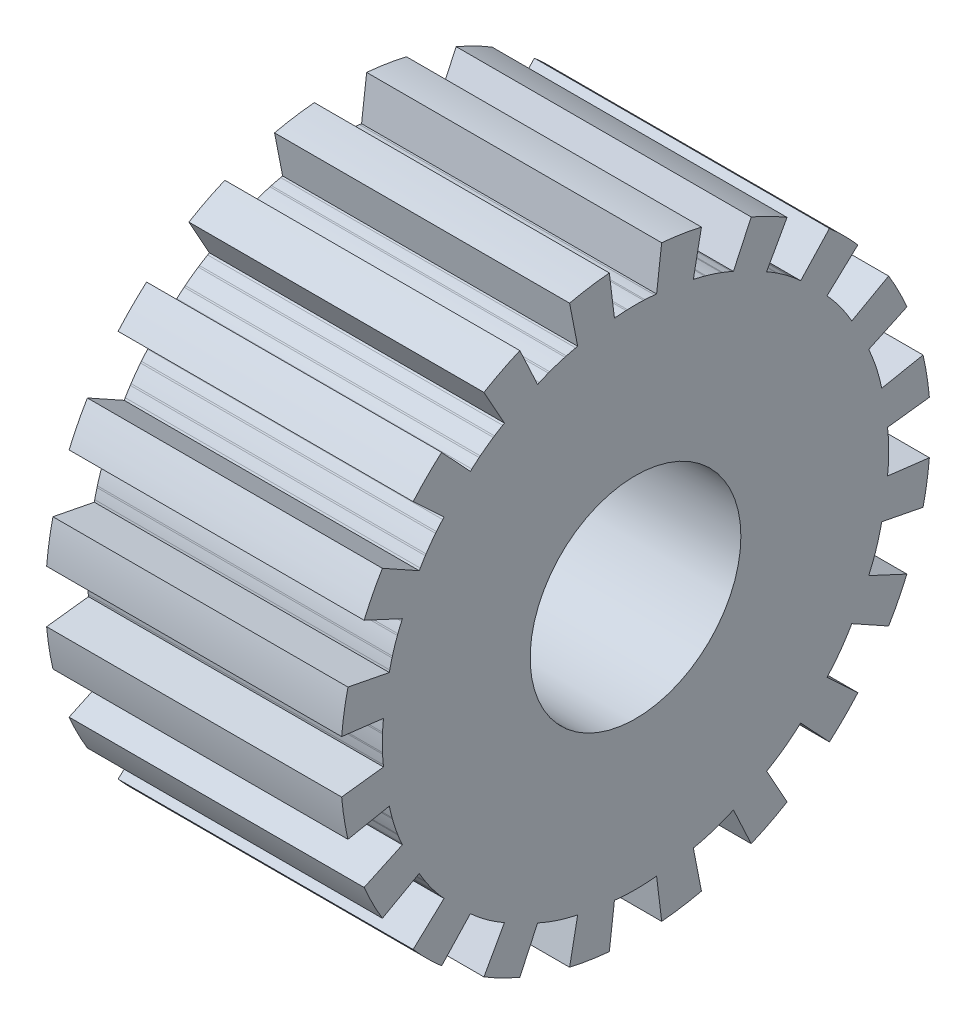
SolidWorks part; units mm, degrees
ref_plane "Front Plane" through (0, 0, 0) normal (0, 0, 1) x (1, 0, 0)
ref_plane "Top Plane" through (0, 0, 0) normal (0, 1, 0) x (1, 0, 0)
ref_plane "Right Plane" through (0, 0, 0) normal (1, 0, 0) x (0, 0, -1)
sketch "Sketch1" plane through (0, 0, 0) normal (1, 0, 0) x (0, 0, -1)
  circle A0 centre (0, 0) radius 70
  circle A1 centre (0, 0) radius 25
  dimension "D1" = 140
  dimension "D2" = 50
extrude "Boss-Extrude1" add sketch "Sketch1" along normal mid plane 70
sketch "Sketch2" plane through (35, 0, 0) normal (1, 0, 0) x (0, 0, -1)
  line L0 (0, 0) -> (0, 107.7478) construction
  line L1 (0, 60.1235) -> (-3.3872, 59.9613)
  line L2 (0, 60.1235) -> (3.3872, 59.9613)
  line L11 (-5, 59.7913) -> (-3.3872, 59.9613)
  line L12 (-5, 59.7913) -> (-9.5713, 97.3774)
  line L13 (5, 59.7913) -> (9.5713, 97.3774)
  line L14 (-9.5713, 97.3774) -> (9.5713, 97.3774)
  line L15 (5, 59.7913) -> (3.3872, 59.9613)
  circle A0 centre (0, 0) radius 60 construction
  point P10 (0, 60)
  point P12 (0, 0)
  point P13 (0, 60.1235)
  point P14 (-3.5437, 59.948)
  dimension "D1" = 120
extrude "Cut-Extrude1" cut sketch "Sketch2" against normal through all
fillet "Fillet2" radius 40 3 edges at (0, 59.9613, -3.3872) (0, 59.9613, 3.3872) (0, 60.1235, 0)
pattern_circular "CirPattern2" count 20 over 360 about axis through (35, 0, 0) along (1, 0, 0) of "Fillet2", "Cut-Extrude1"
